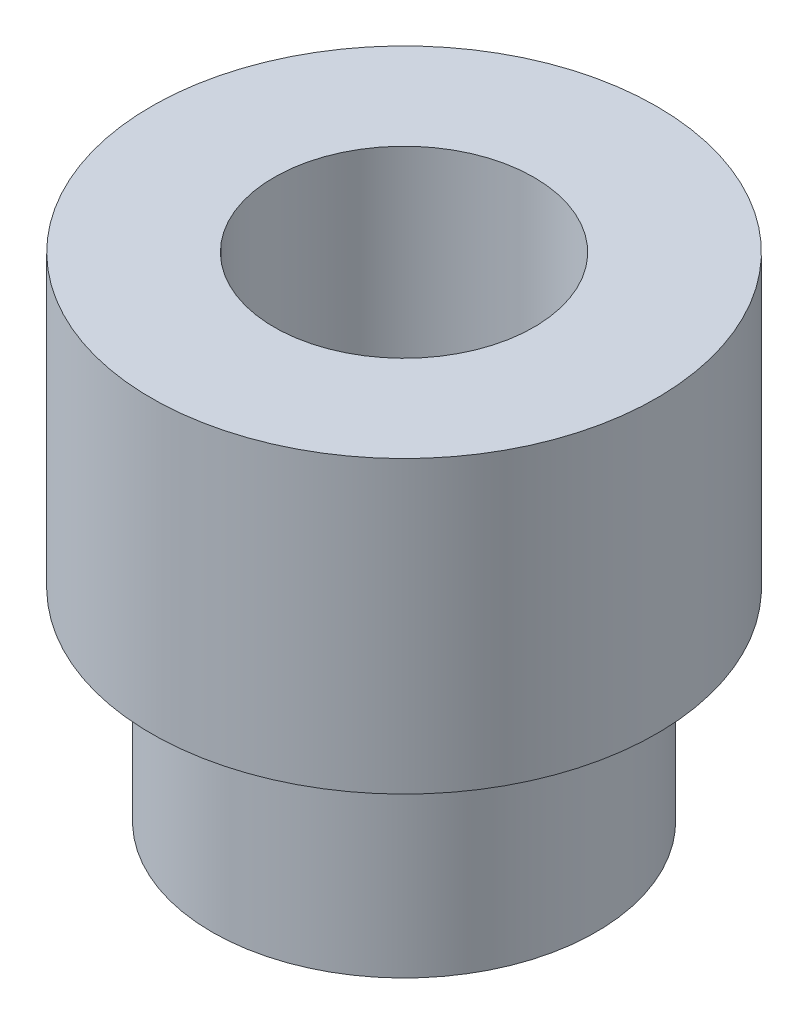
SolidWorks part; units mm, degrees
ref_plane "Front Plane" through (0, 0, 0) normal (0, 0, 1) x (1, 0, 0)
ref_plane "Top Plane" through (0, 0, 0) normal (0, 1, 0) x (1, 0, 0)
ref_plane "Right Plane" through (0, 0, 0) normal (1, 0, 0) x (0, 0, -1)
sketch "Sketch1" plane through (0, 0, 0) normal (0, 1, 0) x (1, 0, 0)
  circle A0 centre (0, 0) radius 3.2639
  circle A1 centre (0, 0) radius 6.35
  circle A2 centre (0, 0) radius 4.826
  dimension "D1" = 6.5278
  dimension "D2" = 12.7
  dimension "D3" = 9.652
extrude "Boss-Extrude1" add sketch "Sketch1" along normal blind 7.3025 contours A1 A2 | A2 A0 region at (-6.1704, 0, 0) region at (-4.6895, 0, 0)
extrude "Boss-Extrude2" add sketch "Sketch1<3>" against normal blind 5.08 contours A2 A0 region at (-4.6895, 0, 0)
sketch "Sketch1<3>" plane through (0, 0, 0) normal (0, 1, 0) x (1, 0, 0) same geometry as "Sketch1"
